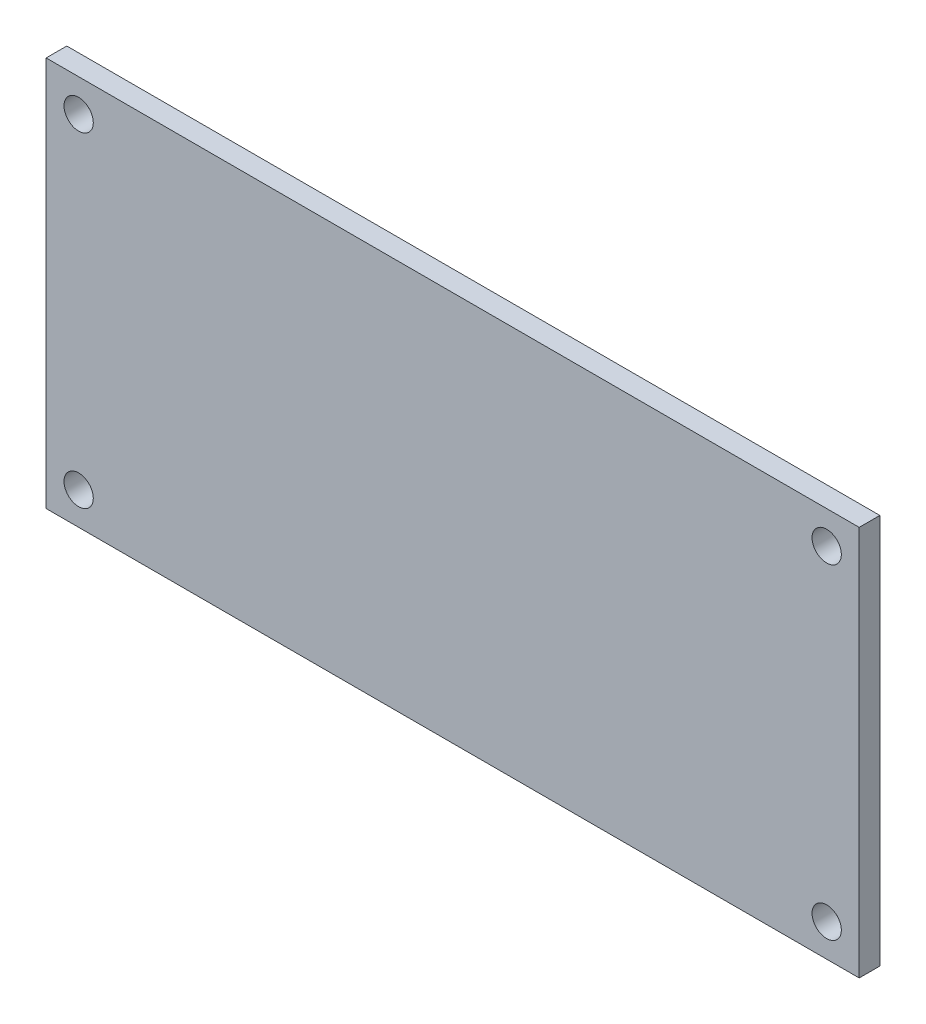
SolidWorks part; units mm, degrees
ref_plane "Plan de face" through (0, 0, 0) normal (0, 0, 1) x (1, 0, 0)
ref_plane "Plan de dessus" through (0, 0, 0) normal (0, 1, 0) x (1, 0, 0)
ref_plane "Plan de droite" through (0, 0, 0) normal (1, 0, 0) x (0, 0, -1)
sketch "Sketch1" plane through (0, 0, 0) normal (0, 0, 1) x (1, 0, 0)
  line L1 (62.5, -30) -> (-62.5, -30)
  line L2 (62.5, -30) -> (62.5, 30)
  line L3 (62.5, 30) -> (-62.5, 30)
  line L4 (-62.5, -30) -> (-62.5, 30)
  line L5 (62.5, -30) -> (-62.5, 30) construction
  line L6 (62.5, 30) -> (-62.5, -30) construction
  point P0 (0, 0)
  dimension "D1" = 125
  dimension "D2" = 60
extrude "Boss-Extrude1" add sketch "Sketch1" along normal blind 3.175
sketch "Sketch2" plane through (0, 0, 3.175) normal (0, 0, 1) x (1, 0, 0)
  line L0 (0, -30) -> (0, 30) construction
  line L1 (-62.5, -30) -> (62.5, -30) construction
  line L2 (62.5, 30) -> (-62.5, 30) construction
  line L3 (-62.5, 30) -> (-62.5, -30) construction
  circle A0 centre (-57.5, 25) radius 2.25
  circle A1 centre (-57.5, -25) radius 2.25
  circle A4 centre (57.5, -25) radius 2.25
  circle A5 centre (57.5, 25) radius 2.25
  point P14 (0, 0)
  point P15 (-58.6715, -27.0158)
  dimension "D5" = 4.5
  dimension "D6" = 4.5
  dimension "D1" = 5
  dimension "D2" = 5
  dimension "D3" = 5
  dimension "D4" = 5
extrude "Cut-Extrude2" cut sketch "Sketch2" against normal blind 3.175
